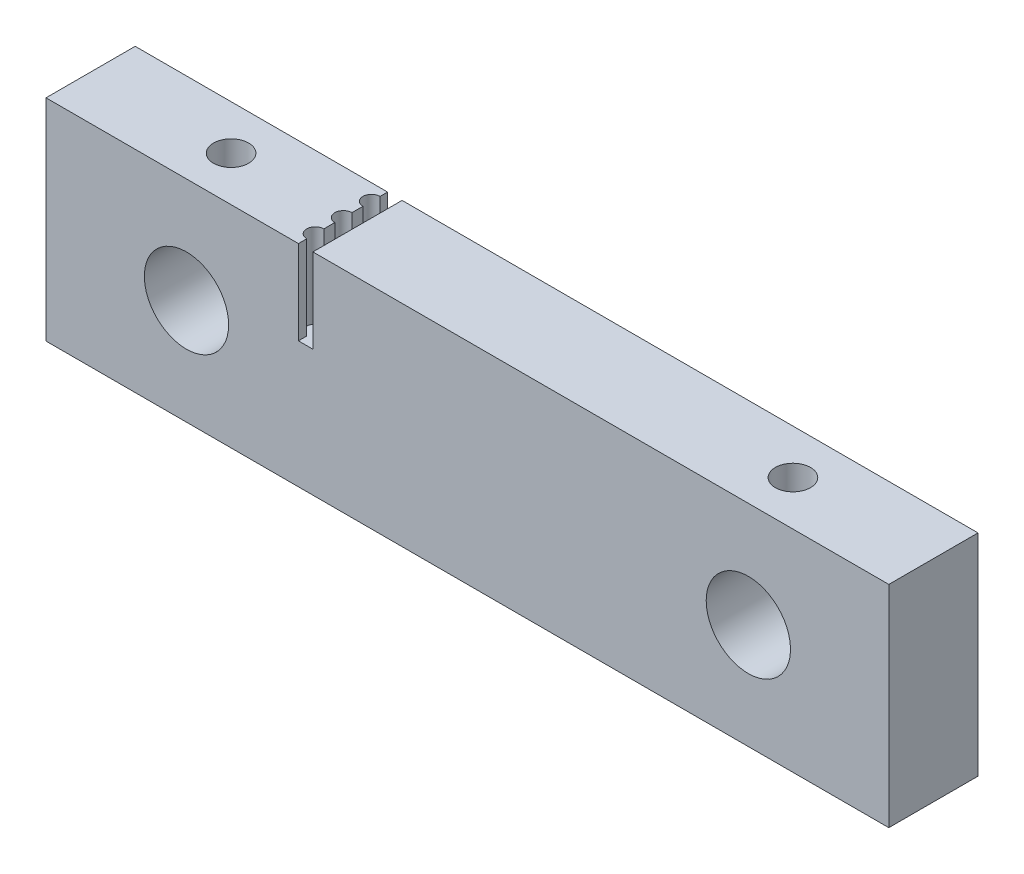
SolidWorks part; units mm, degrees
material "6061 Alloy"
ref_plane "Front Plane" through (0, 0, 0) normal (0, 0, 1) x (1, 0, 0)
ref_plane "Top Plane" through (0, 0, 0) normal (0, 1, 0) x (1, 0, 0)
ref_plane "Right Plane" through (0, 0, 0) normal (1, 0, 0) x (0, 0, -1)
sketch "Sketch1" plane through (0, 0, 0) normal (0, 0, 1) x (1, 0, 0)
  line L0 (30, 15) -> (30, 0) construction
  line L1 (0, 0) -> (60, 0)
  line L2 (0, 0) -> (0, 15)
  line L3 (0, 15) -> (60, 15)
  line L4 (60, 0) -> (60, 15)
  line L5 (0, 7.5) -> (60, 7.5) construction
  circle A0 centre (10, 7.5) radius 3
  circle A1 centre (50, 7.5) radius 3
  dimension "D3" = 6
  dimension "D1" = 60
  dimension "D2" = 15
  dimension "D4" = 40
extrude "Boss-Extrude1" add sketch "Sketch1" along normal blind 6.35
ref_axis "Axis1" through (10, 7.5, 6.35) along (0, 0, -1)
hole_wizard "M3 Tapped Hole1" positions "Sketch4" profile "Sketch3" tap size "M3" standard "ISO"
sketch "Sketch4" plane through (0, 15, 0) normal (0, 1, 0) x (-1, 0, 0)
  line L0 (0, 3.175) -> (-60, 3.175) construction
  line L1 (0, 6.35) -> (0, 0) construction
  line L2 (-60, 6.35) -> (-60, 0) construction
  line L5 (-30, 0) -> (-30, 6.35) construction
  line L6 (-60, 0) -> (0, 0) construction
  line L7 (-60, 6.35) -> (0, 6.35) construction
  line L10 (-10, 6.35) -> (-10, 0) construction
  point P0 (-10, 3.175)
  point P25 (-50, 3.175)
sketch "Sketch3" plane through (10, 15, 3.175) normal (1, 0, 0) x (0, 0, 1)
  line L0 (0, 0) -> (0, 9.2511)
  line L1 (0, 9.2511) -> (1.25, 8.5)
  line L2 (1.25, 8.5) -> (1.25, 0)
  line L5 (1.25, 0) -> (0, 0)
  line L10 (0, 9.2511) -> (-1.25, 8.5) construction
  line L11 (0, -6.35) -> (0, 107.95) construction
  dimension "Tap Drill Dia." = 2.5
  dimension "Tap Drill Depth" = 8.5
  dimension "Drill Angle" = 118
cosmetic thread "Hole Thread1" parameters "D1"=4.8642, "D2"=3
cosmetic thread "Hole Thread2" parameters "D1"=4.8642, "D2"=3
ref_plane "Plane1" through (30, 0, 0) normal (-1, 0, 0) x (0, 0, 1)
sketch "Sketch5" plane through (0, 15, 0) normal (0, 1, 0) x (1, 0, 0)
  line L0 (19, -6.35) -> (19, 0) construction
  line L1 (60, -6.35) -> (0, -6.35) construction
  line L2 (60, 0) -> (0, 0) construction
  line L3 (19, -6.35) -> (19, 0)
  line L4 (19, 0) -> (17.97, 0)
  line L5 (17.97, 0) -> (17.97, -0.5375)
  line L6 (17.97, -1.7575) -> (17.97, -2.5375)
  line L7 (17.97, -3.7575) -> (17.97, -4.5375)
  line L8 (17.97, -5.7575) -> (17.97, -6.35)
  line L9 (17.97, -6.35) -> (19, -6.35)
  line L10 (0, -6.35) -> (0, 0) construction
  arc A3 (17.97, -0.5375) -> (17.97, -1.7575) centre (17.97, -1.1475) ccw
  arc A4 (17.97, -2.5375) -> (17.97, -3.7575) centre (17.97, -3.1475) ccw
  arc A5 (17.97, -4.5375) -> (17.97, -5.7575) centre (17.97, -5.1475) ccw
  dimension "D1" = 2
  dimension "D4" = 0.61
  dimension "D2" = 2
  dimension "D3" = 1.03
  dimension "D5" = 19
extrude "Cut-Extrude1" cut sketch "Sketch5" against normal blind 6
